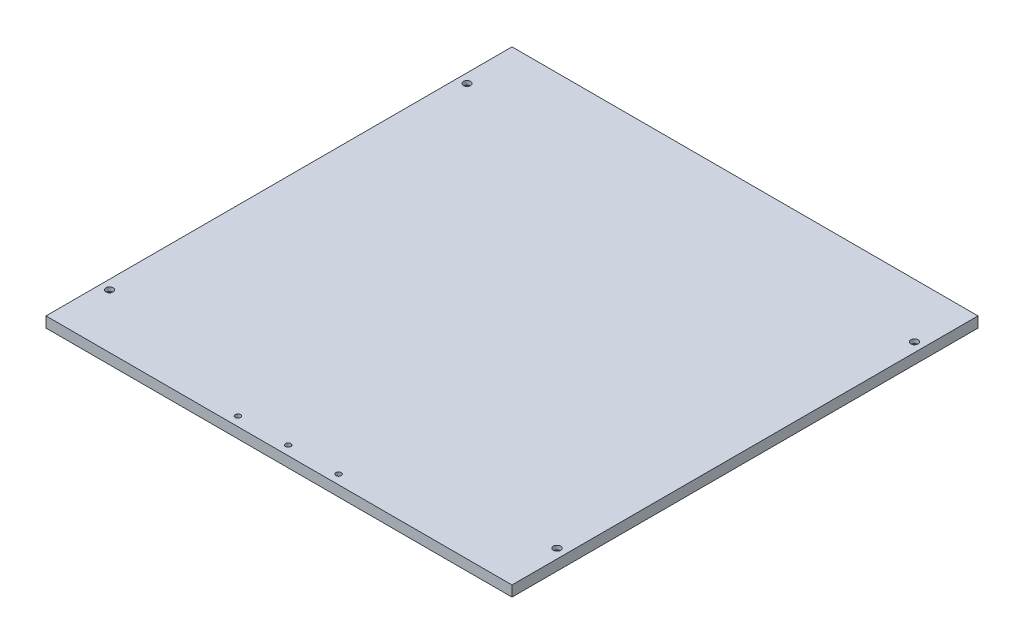
SolidWorks part; units mm, degrees
ref_plane "Front Plane" through (0, 0, 0) normal (0, 0, 1) x (1, 0, 0)
ref_plane "Top Plane" through (0, 0, 0) normal (0, 1, 0) x (1, 0, 0)
ref_plane "Right Plane" through (0, 0, 0) normal (1, 0, 0) x (0, 0, -1)
sketch "PlateSketch2" plane through (0, 0, 0) normal (0, 1, 0) x (1, 0, 0)
  line L1 (0, 0) -> (352, 0)
  line L2 (0, 0) -> (0, 352)
  line L3 (0, 352) -> (352, 352)
  line L4 (352, 0) -> (352, 352)
  circle A0 centre (7, 311) radius 2
  circle A1 centre (345, 311) radius 2
  circle A2 centre (138, 7) radius 2
  circle A3 centre (176, 7) radius 2
  circle A4 centre (214, 7) radius 2
  circle A5 centre (7, 41) radius 2
  circle A6 centre (345, 41) radius 2
  dimension "D5" = 4
  dimension "D10" = 4
  dimension "D1" = 352
  dimension "D2" = 352
  dimension "D3" = 7
  dimension "D4" = 7
  dimension "D6" = 41
  dimension "D7" = 38
  dimension "D8" = 38
  dimension "D9" = 176
  dimension "D11" = 7
  dimension "D12" = 41
extrude "Boss-Extrude1" add sketch "PlateSketch2" along normal blind 8
sketch "BoreSketch1" plane through (0, 8, 0) normal (0, 1, 0) x (1, 0, 0)
  circle A0 centre (7, 311) radius 2.75
  circle A1 centre (345, 311) radius 2.75
  circle A4 centre (7, 311) radius 2 construction
  circle A5 centre (345, 311) radius 2 construction
  circle A6 centre (7, 41) radius 2.75
  circle A7 centre (345, 41) radius 2.75
  dimension "D1" = 5.5
extrude "BoreCut-Extrude1" cut sketch "BoreSketch1" against normal blind 3
equation "\"BuildPlateStandoffHolesDistanceFromLeftOrRightSide\"= 7mm"
equation "\"BuildPlateStandoffHolesDistanceFromBackSide\"= 41mm"
equation "\"BedSpringHoleSize\"= \"M4HoleDiameter\""
equation "\"BuildPlateWidth\"= 352mm'Spec"
equation "\"BuildPlateLength\"= 352mm'Spec"
equation "\"D5@PlateSketch2\" = \"BedSpringHoleSize\""
equation "\"D10@PlateSketch2\" = \"BedSpringHoleSize\""
equation "\"BuildPlateBoreDiameter\"= \"M4BoreDiameter\"'Spec"
equation "\"D1@BoreSketch1\" = \"BuildPlateBoreDiameter\""
equation "\"BuildPlateBoreDepth\"= 3mm'Spec"
equation "\"D1@BoreCut-Extrude1\" = \"BuildPlateBoreDepth\""
equation "\"BuildPlateDepth\"= 8mm'Spec"
equation "\"D1@Boss-Extrude1\"=\"BuildPlateDepth\""
equation "\"D1@PlateSketch2\"= \"BuildPlateLength\""
equation "\"D2@PlateSketch2\"=\"BuildPlateWidth\""
equation "\"D9@PlateSketch2\"=\"BuildPlateWidth\"/2"
equation "\"BuildPlateFlankingHoles\"= 38mm"
equation "\"D7@PlateSketch2\"=\"BuildPlateFlankingHoles\""
equation "\"D6@PlateSketch2\"=\"BuildPlateStandoffHolesDistanceFromBackSide\""
equation "\"D3@PlateSketch2\"=\"BuildPlateStandoffHolesDistanceFromLeftOrRightSide\""
equation "\"D4@PlateSketch2\"=\"BuildPlateStandoffHolesDistanceFromLeftOrRightSide\""
equation "\"BuildPlateStandoffHolesDistanceFromFront\"= 7mm"
equation "\"D11@PlateSketch2\"=\"BuildPlateStandoffHolesDistanceFromFront\""
equation "\"D12@PlateSketch2\"=\"BuildPlateStandoffHolesDistanceFromBackSide\""
equation "\"M4HoleDiameter\"= 4mm"
equation "\"M4FlatHeadBoreDepth\"= .65mm"
equation "\"M4BoreDiameter\"= 5.5mm"
